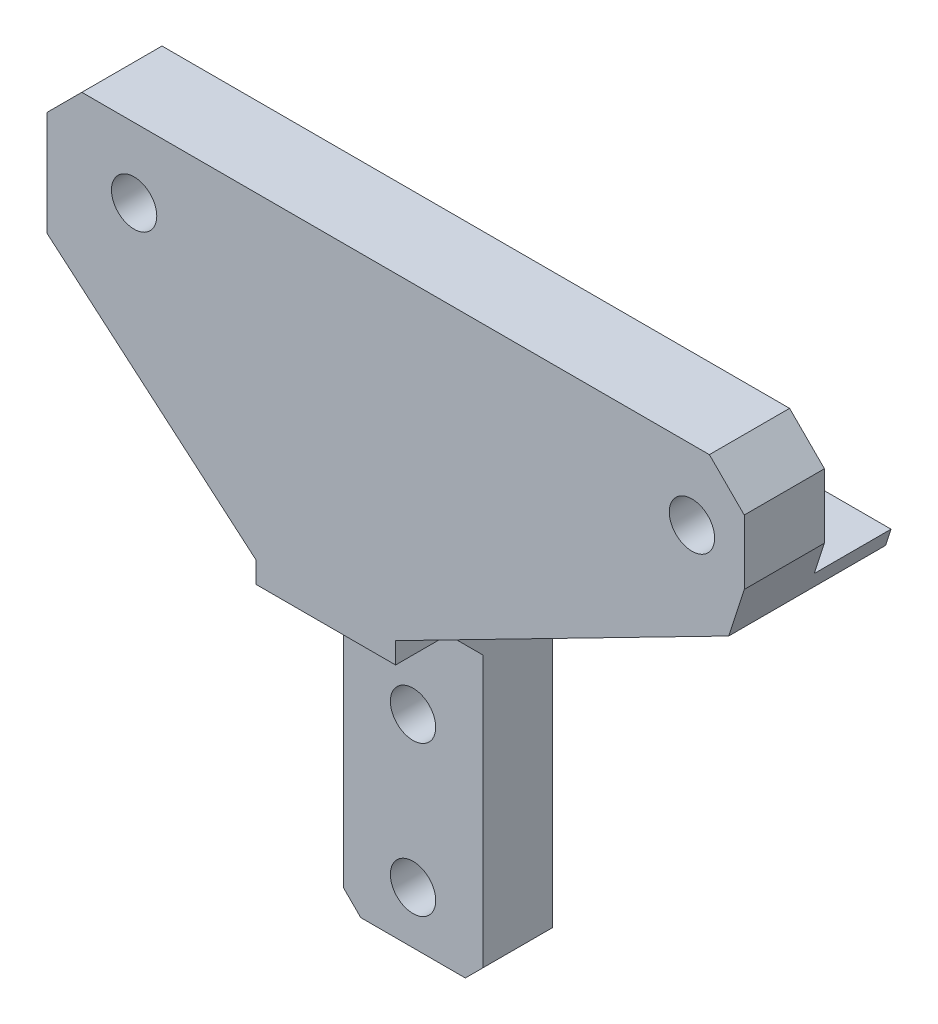
SolidWorks part; units mm, degrees
ref_plane "前视基准面" through (0, 0, 0) normal (0, 0, 1) x (1, 0, 0)
ref_plane "上视基准面" through (0, 0, 0) normal (0, 1, 0) x (1, 0, 0)
ref_plane "右视基准面" through (0, 0, 0) normal (1, 0, 0) x (0, 0, -1)
other "Configuration Table"
sketch "草图1" plane through (0, 0, 0) normal (0, 0, 1) x (1, 0, 0)
  line L1 (-10, 2) -> (10, 2)
  line L2 (-10, 2) -> (-10, -2)
  line L4 (10, 2) -> (10, -2)
  line L5 (-10, 2) -> (10, -2) construction
  line L6 (-10, -2) -> (10, 2) construction
  line L8 (-4, -7.1203) -> (-4, -17)
  line L9 (-4, -17) -> (0, -17)
  line L10 (0, -7.1203) -> (0, -17)
  line L11 (-10, -2) -> (-4, -7.1203)
  line L12 (0, -7.1203) -> (10, -2)
  circle A0 centre (-7.5, 0) radius 0.65
  circle A1 centre (8.5, 0) radius 0.65
  circle A2 centre (-2, -15.5) radius 0.65
  circle A3 centre (-2, -11.2) radius 0.65
  point P0 (0, 0)
  dimension "D5" = 1.3
  dimension "D7" = 1.3
  dimension "D12" = 1.3
  dimension "D13" = 1.3
  dimension "D1" = 20
  dimension "D2" = 4
  dimension "D3" = 4
  dimension "D6" = 2.5
  dimension "D8" = 1.5
  dimension "D9" = 10
  dimension "D10" = 2
  dimension "D11" = 2
  dimension "D14" = 2
  dimension "D15" = 2
  dimension "D16" = 1.5
  dimension "D17" = 4.3
extrude "凸台-拉伸2" add sketch "草图1" along normal blind 5.5
sketch "草图3" plane through (0, 0, 5.5) normal (0, 0, -1) x (-1, 0, 0)
  line L0 (0, -7.7252) -> (4, -7.7252)
  line L8 (-10, 2) -> (-10, -2)
  line L9 (-10, -2) -> (0, -7.1203)
  line L10 (0, -7.1203) -> (0, -17)
  line L11 (0, -17) -> (4, -17)
  line L12 (4, -17) -> (4, -7.1203)
  line L14 (10, -2) -> (10, 2)
  line L15 (10, 2) -> (-10, 2)
  line L18 (0, -7.7252) -> (0, -17)
  line L19 (0, -17) -> (4, -17)
  line L20 (4, -17) -> (4, -7.7252)
  line L25 (4, -7.1203) -> (10, -2)
  circle A0 centre (2, -15.5) radius 0.65 construction
  circle A1 centre (2, -11.2) radius 0.65 construction
  circle A2 centre (2, -15.5) radius 0.65
  circle A3 centre (2, -11.2) radius 0.65
  dimension "D1" = 0
extrude "切除-拉伸2" cut sketch "草图3" along normal blind 2.5
chamfer "倒角1" distance 1 angle 45 1 edges at (-2, -7.7252, 3)
chamfer "倒角2" distance 1 angle 45 2 edges at (-10, 2, 2.75) (10, 2, 2.75)
chamfer "倒角3" distance 0.5 angle 45 2 edges at (-4, -17, 1.5) (0, -17, 1.5)
sketch "草图4" plane through (0, 0, 0) normal (0, 0, 1) x (1, 0, 0)
  line L6 (-10, -1.7462) -> (10, -1.7462)
  line L12 (-4, -7.1203) -> (-4, -7.7252)
  line L13 (-4, -7.7252) -> (0, -7.7252)
  line L16 (0, -7.7252) -> (0, -7.1203)
  line L17 (0, -7.1203) -> (10, -2)
  line L18 (10, -2) -> (10, 1)
  line L19 (10, 1) -> (9, 2)
  line L20 (9, 2) -> (-9, 2)
  line L21 (-9, 2) -> (-10, 1)
  line L22 (-10, 1) -> (-10, -2)
  line L23 (-10, -2) -> (-4, -7.1203)
  line L30 (10, -1.7462) -> (10, 1)
  line L31 (10, 1) -> (9, 2)
  line L32 (9, 2) -> (-9, 2)
  line L33 (-9, 2) -> (-10, 1)
  line L34 (-10, 1) -> (-10, -1.7462)
  circle A0 centre (8.5, 0) radius 0.65 construction
  circle A1 centre (-7.5, 0) radius 0.65 construction
  circle A2 centre (8.5, 0) radius 0.65
  circle A3 centre (-7.5, 0) radius 0.65
  dimension "D1" = 0
extrude "切除-拉伸3" cut sketch "草图4" along normal blind 3.2
chamfer "倒角4" distance 0.5 angle 45 1 edges at (10, -2, 2.75) first distance on face at (5, -4.5601, 2.75)
sketch "草图5" plane through (0, 0, 0) normal (0, 0, -1) x (-1, 0, 0)
  line L8 (10, -1.7462) -> (-9.7104, -1.7462)
  line L12 (-9.7104, -1.7462) -> (-9.5549, -2.2279)
  line L13 (-9.5549, -2.2279) -> (0, -7.1203)
  line L14 (0, -7.1203) -> (0, -16.5)
  line L15 (0, -16.5) -> (0.5, -17)
  line L16 (4, -16.5) -> (4, -7.1203)
  line L17 (4, -7.1203) -> (10, -2)
  line L18 (10, -2) -> (10, -1.7462)
  line L23 (-9.7104, -1.7462) -> (-9.5549, -2.2279)
  line L24 (-9.5549, -2.2279) -> (0, -7.1203)
  line L25 (0, -7.1203) -> (0, -16.5)
  line L27 (4, -16.5) -> (4, -7.1203)
  line L28 (4, -7.1203) -> (10, -2)
  line L29 (10, -2) -> (10, -1.7462)
  line L36 (0, -16.5) -> (0.5, -17)
  line L39 (0.5, -17) -> (3.5, -17)
  line L41 (0.5, -17) -> (3.5, -17)
  line L43 (3.5, -17) -> (4, -16.5)
  line L44 (3.5, -17) -> (4, -16.5)
  line L45 (10, -1.7462) -> (-9.7104, -1.7462)
  circle A0 centre (7.5, 0) radius 0.65 construction
  circle A1 centre (-8.5, 0) radius 0.65 construction
  circle A2 centre (7.5, 0) radius 0.65
  circle A3 centre (-8.5, 0) radius 0.65
  dimension "D1" = 0
extrude "切除-拉伸4" cut sketch "草图5" against normal blind 1
